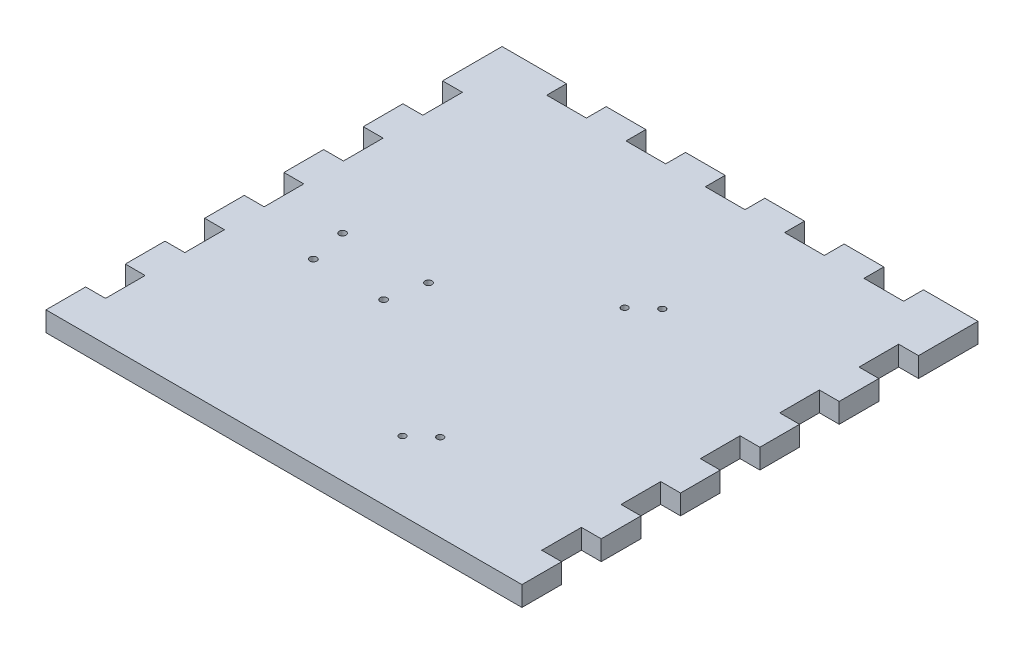
SolidWorks part; units mm, degrees
ref_plane "Front Plane" through (0, 0, 0) normal (0, 0, 1) x (1, 0, 0)
ref_plane "Top Plane" through (0, 0, 0) normal (0, 1, 0) x (1, 0, 0)
ref_plane "Right Plane" through (0, 0, 0) normal (1, 0, 0) x (0, 0, -1)
sketch "Sketch1" plane through (0, 0, 0) normal (0, 1, 0) x (1, 0, 0)
  line L1 (-139.7, -139.7) -> (139.7, -139.7)
  line L2 (-139.7, -139.7) -> (-139.7, 139.7)
  line L3 (-139.7, 139.7) -> (139.7, 139.7)
  line L4 (139.7, -139.7) -> (139.7, 139.7)
  line L5 (-139.7, -139.7) -> (139.7, 139.7) construction
  line L6 (-139.7, 139.7) -> (139.7, -139.7) construction
  point P0 (0, 0)
  dimension "D1" = 279.4
  dimension "D2" = 279.4
extrude "Boss-Extrude1" add sketch "Sketch1" along normal blind 12.7
sketch "Sketch2" plane through (139.7, 0, 0) normal (1, 0, 0) x (0, 0, -1)
  line L0 (-139.7, 12.7) -> (139.7, 12.7) construction
  line L1 (-139.7, 0) -> (-114.3, 0)
  line L2 (-139.7, 0) -> (-139.7, 12.7)
  line L3 (-139.7, 12.7) -> (-114.3, 12.7)
  line L4 (-114.3, 0) -> (-114.3, 12.7)
  dimension "D1" = 25.4
extrude "Boss-Extrude2" add sketch "Sketch2" along normal blind 12.7
pattern_linear "LPattern1" count 6 spacing 50.8 along (0, 0, -1) of "Boss-Extrude2"
mirror "Mirror1" about plane through (0, 0, 0) normal (1, 0, 0) of "LPattern1"
sketch "Sketch3" plane through (0, 0, -139.7) normal (0, 0, -1) x (-1, 0, 0)
  line L0 (-152.4, 12.7) -> (152.4, 12.7) construction
  line L1 (-142.875, 12.7) -> (-117.475, 12.7)
  line L2 (-142.875, 12.7) -> (-142.875, 0)
  line L3 (-142.875, 0) -> (-117.475, 0)
  line L4 (-117.475, 12.7) -> (-117.475, 0)
  line L5 (-152.4, 0) -> (152.4, 0) construction
  line L6 (-152.4, 0) -> (-152.4, 12.7) construction
  dimension "D1" = 9.525
  dimension "D2" = 25.4
extrude "Boss-Extrude3" add sketch "Sketch3" along normal blind 12.7
pattern_linear "LPattern2" count 6 spacing 50.8 along (-1, 0, 0) of "Boss-Extrude3"
sketch "Sketch5" plane through (0, 0, -139.7) normal (0, 0, -1) x (-1, 0, 0)
  line L11 (160.655, 0) -> (-160.655, 0) construction
  line L12 (-152.4, 12.7) -> (-127, 12.7)
  line L13 (-152.4, 12.7) -> (-152.4, 0)
  line L14 (-152.4, 0) -> (-127, 0)
  line L15 (-127, 12.7) -> (-127, 0)
  dimension "D1" = 25.4
extrude "Boss-Extrude4" add sketch "Sketch5" along normal blind 12.7
mirror "Mirror2" about plane through (0, 0, 0) normal (1, 0, 0) of "Boss-Extrude4"
sketch "Sketch6" plane through (0, 0, 0) normal (0, -1, 0) x (1, 0, 0)
  circle A0 centre (44.45, -58.1456) radius 2.1 construction
  circle A1 centre (44.45, -58.1456) radius 2.1
  circle A2 centre (31.75, -46.7156) radius 2.1 construction
  circle A3 centre (31.75, -46.7156) radius 2.1
  circle A4 centre (31.75, 95.5244) radius 2.1 construction
  circle A5 centre (31.75, 95.5244) radius 2.1
  circle A6 centre (44.45, 84.0944) radius 2.1 construction
  circle A7 centre (44.45, 84.0944) radius 2.1
extrude "Cut-Extrude1" cut sketch "Sketch6" against normal through all
sketch "Sketch7" plane through (0, 0, 0) normal (0, -1, 0) x (1, 0, 0)
  circle A0 centre (31.75, 95.5244) radius 4.318
  circle A1 centre (31.75, 95.5244) radius 2.1 construction
  circle A2 centre (44.45, 84.0944) radius 4.318
  circle A3 centre (31.75, -46.7156) radius 4.318
  circle A4 centre (44.45, -58.1456) radius 4.318
  dimension "D1" = 8.636
  dimension "D2" = 8.636
  dimension "D3" = 8.636
  dimension "D4" = 8.636
extrude "Cut-Extrude2" cut sketch "Sketch7" against normal blind 6.35
sketch "Sketch8" plane through (0, 12.7, 0) normal (0, 1, 0) x (1, 0, 0)
  circle A0 centre (-49.9203, -25.9489) radius 2.2225 construction
  circle A1 centre (-49.9203, -25.9489) radius 2.2225
  circle A2 centre (-44.9203, -2.2189) radius 2.2225 construction
  circle A3 centre (-44.9203, -2.2189) radius 2.2225
  circle A4 centre (-94.9203, -25.9489) radius 2.2225 construction
  circle A5 centre (-94.9203, -25.9489) radius 2.2225
  circle A6 centre (-99.9203, -2.2189) radius 2.2225 construction
  circle A7 centre (-99.9203, -2.2189) radius 2.2225
extrude "Cut-Extrude3" cut sketch "Sketch8" against normal through all
sketch "Sketch9" plane through (0, 0, 0) normal (0, -1, 0) x (1, 0, 0)
  circle A0 centre (-94.9203, 25.9489) radius 6.35
  circle A1 centre (-99.9203, 2.2189) radius 6.35
  circle A2 centre (-44.9203, 2.2189) radius 6.35
  circle A3 centre (-49.9203, 25.9489) radius 6.35
  dimension "D1" = 12.7
  dimension "D2" = 12.7
  dimension "D3" = 12.7
  dimension "D4" = 12.7
extrude "Cut-Extrude4" cut sketch "Sketch9" against normal blind 6.35
